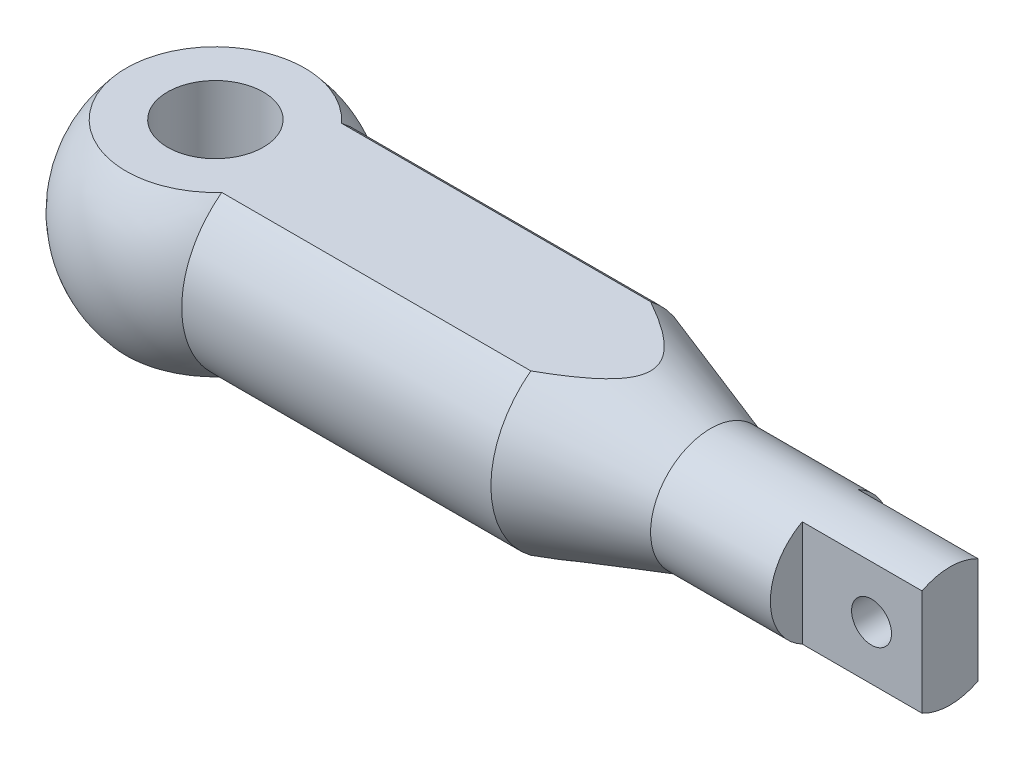
SolidWorks part; units mm, degrees
ref_plane "Front Plane" through (0, 0, 0) normal (0, 0, 1) x (1, 0, 0)
ref_plane "Top Plane" through (0, 0, 0) normal (0, 1, 0) x (1, 0, 0)
ref_plane "Right Plane" through (0, 0, 0) normal (1, 0, 0) x (0, 0, -1)
sketch "Sketch23" plane through (0, 0, 0) normal (0, 1, 0) x (1, 0, 0)
  line L0 (-139.6245, 21.6387) -> (-139.6245, -8.3613)
  arc A0 (-139.6245, 21.6387) -> (-139.6245, -8.3613) centre (-139.6245, 6.6387) ccw
revolve "Revolve5" add sketch "Sketch23" angle 360 about L0
sketch "Sketch24" plane through (0, 0, 0) normal (0, 1, 0) x (1, 0, 0)
  line L1 (-139.6245, -5.8613) -> (-92.6245, -5.8613)
  line L2 (-92.6245, -5.8613) -> (-92.6245, 6.6387)
  line L5 (-92.6245, 6.6387) -> (-139.6245, 6.6387)
  line L6 (-139.6245, 6.6387) -> (-139.6245, -5.8613)
revolve "Revolve6" add sketch "Sketch24" angle 360 about L5
sketch "Sketch25" plane through (0, 0, 0) normal (0, 1, 0) x (1, 0, 0)
  line L1 (-92.6245, -5.8613) -> (-92.6245, 6.6387)
  line L3 (-77.6245, -0.8613) -> (-77.6245, 6.6387)
  line L5 (-92.6245, -5.8613) -> (-77.6245, -0.8613)
  line L6 (-77.6245, 6.6387) -> (-92.6245, 6.6387)
revolve "Revolve7" add sketch "Sketch25" angle 360 about L6
sketch "Sketch26" plane through (-77.6245, 0, 0) normal (1, 0, 0) x (0, 0, -1)
  line L1 (3.1387, 6.6332) -> (3.1387, -6.6332)
  line L3 (10.1387, 6.6332) -> (10.1387, -6.6332)
  circle A0 centre (6.6387, 0) radius 7.5
  circle M4 centre (6.6387, 0) radius 7.5
extrude "Boss-Extrude8" add sketch "Sketch26" along normal blind 15 contours L1 M4 | L3 M4 region at (-77.6245, 0, -1.4953) region at (-77.6245, 0, -11.782)
extrude "Boss-Extrude9" add sketch "Sketch26<3>" along normal blind 30 contours L3 L1 M4 region at (-77.6245, 0, -6.6387)
sketch "Sketch26<3>" plane through (-77.6245, 0, 0) normal (1, 0, 0) x (0, 0, -1) same geometry as "Sketch26"
sketch "Sketch27" plane through (-47.6245, 0, 0) normal (1, 0, 0) x (0, 0, -1)
  line L1 (6.6387, 10) -> (21.6387, 10)
  line L2 (21.6387, 10) -> (21.6387, 15)
  line L3 (21.6387, 15) -> (-8.3613, 15)
  line L4 (-8.3613, 15) -> (-8.3613, 10)
  line L5 (-8.3613, 10) -> (6.6387, 10)
  line L6 (6.6387, -10) -> (21.6387, -10)
  line L7 (21.6387, -10) -> (21.6387, -15)
  line L8 (21.6387, -15) -> (-8.3613, -15)
  line L9 (-8.3613, -15) -> (-8.3613, -10)
  line L10 (-8.3613, -10) -> (6.6387, -10)
extrude "Cut-Extrude11" cut sketch "Sketch27" against normal blind 129
sketch "Sketch28" plane through (0, 10, 0) normal (0, 1, 0) x (1, 0, 0)
  circle A0 centre (-139.6245, 6.6387) radius 6
extrude "Cut-Extrude12" cut sketch "Sketch28" against normal blind 129
sketch "Sketch29" plane through (0, 0, -3.1387) normal (0, 0, 1) x (1, 0, 0)
  line L0 (-47.6245, 6.6332) -> (-47.6245, -6.6332) construction
  line L1 (-47.6245, 7.5) -> (-77.6245, 7.5) construction
  circle A0 centre (-53.9573, 0.09) radius 2.5
  dimension "D1" = 6.3328
  dimension "D2" = 7.41
extrude "Cut-Extrude13" cut sketch "Sketch29" against normal blind 129
